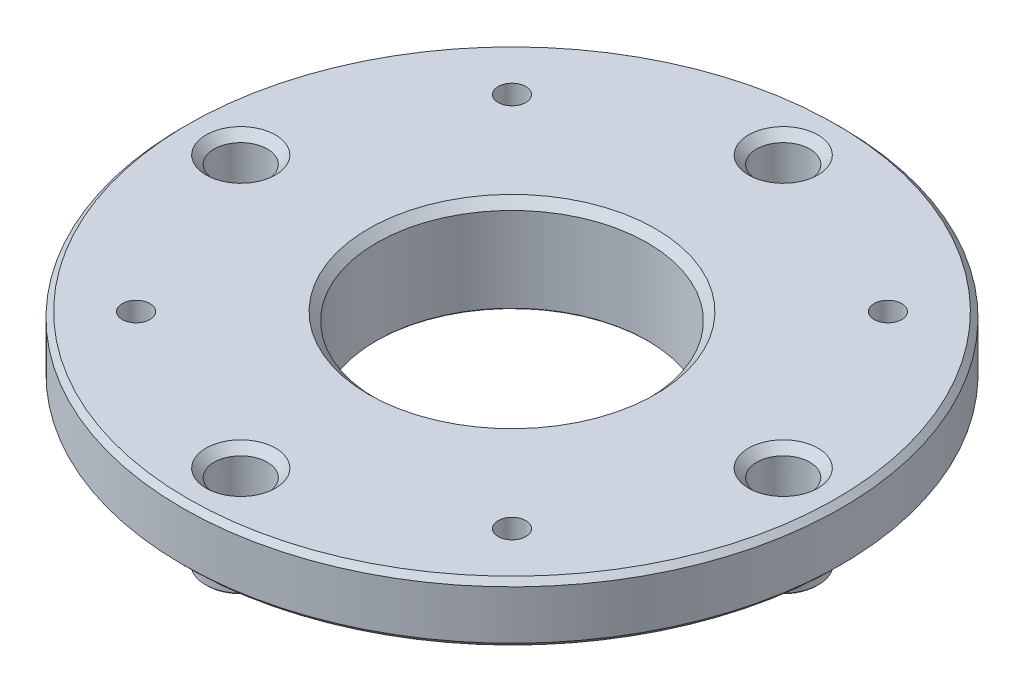
SolidWorks part; units mm, degrees
ref_plane "Front Plane" through (0, 0, 0) normal (0, 0, 1) x (1, 0, 0)
ref_plane "Top Plane" through (0, 0, 0) normal (0, 1, 0) x (1, 0, 0)
ref_plane "Right Plane" through (0, 0, 0) normal (1, 0, 0) x (0, 0, -1)
sketch "Sketch1" plane through (0, 0, 0) normal (0, 0, 1) x (1, 0, 0)
  line L0 (60.75, 11) -> (0, 11)
  line L1 (0, 11) -> (0, 0)
  line L2 (0, 0) -> (60.75, 0)
  line L3 (60.75, 0) -> (60.75, 11)
  line L4 (0, 11) -> (0, 0) construction
revolve "Revolve1" add sketch "Sketch1" angle 360 about L4 reverse direction yes
sketch "Sketch2" plane through (0, 0, 0) normal (0, -1, 0) x (1, 0, 0)
  circle A0 centre (0, 0) radius 28.485
extrude "Boss-Extrude1" add sketch "Sketch2" along normal blind 6.35
ref_plane "Plane1" through (0, 0, 0) normal (0, 0, -1) x (-1, 0, 0)
sketch "Sketch3" plane through (0, 0, 0) normal (0, 0, -1) x (-1, 0, 0)
  line L0 (43.525, -4.65) -> (50, -4.65)
  line L1 (50, -4.65) -> (50, 0)
  line L2 (50, 0) -> (43.525, 0)
  line L3 (43.525, 0) -> (43.525, -4.65)
  line L4 (50, -4.65) -> (50, 0) construction
revolve "Revolve2" add sketch "Sketch3" angle 360 about L4 reverse direction yes
ref_plane "Plane2" through (0, 0, -50) normal (0, 0, -1) x (-1, 0, 0)
sketch "Sketch4" plane through (0, 0, -50) normal (0, 0, -1) x (-1, 0, 0)
  line L0 (-6.475, -4.65) -> (0, -4.65)
  line L1 (0, -4.65) -> (0, 0)
  line L2 (0, 0) -> (-6.475, 0)
  line L3 (-6.475, 0) -> (-6.475, -4.65)
  line L4 (0, -4.65) -> (0, 0) construction
revolve "Revolve3" add sketch "Sketch4" angle 360 about L4 reverse direction yes
sketch "Sketch5" plane through (0, 0, 0) normal (0, 0, -1) x (-1, 0, 0)
  line L0 (-56.475, -4.65) -> (-50, -4.65)
  line L1 (-50, -4.65) -> (-50, 0)
  line L2 (-50, 0) -> (-56.475, 0)
  line L3 (-56.475, 0) -> (-56.475, -4.65)
  line L4 (-50, -4.65) -> (-50, 0) construction
revolve "Revolve4" add sketch "Sketch5" angle 360 about L4 reverse direction yes
ref_plane "Plane3" through (0, 0, 50) normal (0, 0, -1) x (-1, 0, 0)
sketch "Sketch6" plane through (0, 0, 50) normal (0, 0, -1) x (-1, 0, 0)
  line L0 (-6.475, -4.65) -> (0, -4.65)
  line L1 (0, -4.65) -> (0, 0)
  line L2 (0, 0) -> (-6.475, 0)
  line L3 (-6.475, 0) -> (-6.475, -4.65)
  line L4 (0, -4.65) -> (0, 0) construction
revolve "Revolve5" add sketch "Sketch6" angle 360 about L4 reverse direction yes
hole_wizard "Hole1" positions "Sketch8" profile "Sketch7" legacy
sketch "Sketch8" plane through (0, 11, 0) normal (0, 1, 0) x (1, 0, 0)
  point P0 (-34.6482, -34.6482)
  point P1 (34.6482, -34.6482)
  point P2 (34.6482, 34.6482)
  point P3 (-34.6482, 34.6482)
sketch "Sketch7" plane through (-34.6482, 11, 34.6482) normal (1, 0, 0) x (0, 0, 1)
  line L0 (0, 0) -> (0, 17.35)
  line L1 (0, 17.35) -> (2.5527, 17.35)
  line L2 (2.5527, 17.35) -> (2.5527, 0)
  line L3 (2.5527, 0) -> (0, 0)
  line L4 (0, 110) -> (0, -10) construction
  dimension "Diameter" = 5.1054
  dimension "Depth" = 17.35
hole_wizard "M8 Clearance Hole1" positions "Sketch10" profile "Sketch9" hole size "M8" standard "ANSI Metric"
sketch "Sketch10" plane through (0, 11, 0) normal (0, 1, 0) x (1, 0, 0)
  point P0 (50, 0)
  point P1 (0, -50)
  point P2 (-50, 0)
sketch "Sketch9" plane through (50, 11, 0) normal (1, 0, 0) x (0, 0, 1)
  line L0 (0, 0) -> (0, 17.35)
  line L1 (0, 17.35) -> (4.9022, 17.35)
  line L2 (4.9022, 17.35) -> (4.9022, 0)
  line L5 (4.9022, 0) -> (0, 0)
  line L11 (0, -6.35) -> (0, 107.95) construction
  dimension "Thru Hole Dia." = 9.8044
  dimension "Thru Hole Depth" = 17.35
hole_wizard "M45 Clearance Hole1" positions "Sketch12" profile "Sketch11" hole size "M45" standard "ANSI Metric"
sketch "Sketch12" plane through (0, 11, 0) normal (0, 1, 0) x (1, 0, 0)
  point P0 (0, 0)
sketch "Sketch11" plane through (0, 11, 0) normal (1, 0, 0) x (0, 0, 1)
  line L0 (0, 0) -> (0, 17.35)
  line L1 (0, 17.35) -> (24.9555, 17.35)
  line L2 (24.9555, 17.35) -> (24.9555, 0)
  line L5 (24.9555, 0) -> (0, 0)
  line L11 (0, -6.35) -> (0, 107.95) construction
  dimension "Thru Hole Dia." = 49.911
  dimension "Thru Hole Depth" = 17.35
hole_wizard "M8 Clearance Hole2" positions "Sketch14" profile "Sketch13" hole size "M8" standard "ANSI Metric"
sketch "Sketch14" plane through (0, -4.65, 0) normal (0, -1, 0) x (-1, 0, 0)
  point P0 (0, 50)
sketch "Sketch13" plane through (0, -4.65, -50) normal (1, 0, 0) x (0, 0, -1)
  line L0 (0, 0) -> (0, 15.65)
  line L1 (0, 15.65) -> (4.9022, 15.65)
  line L2 (4.9022, 15.65) -> (4.9022, 0)
  line L5 (4.9022, 0) -> (0, 0)
  line L11 (0, -6.35) -> (0, 107.95) construction
  dimension "Thru Hole Dia." = 9.8044
  dimension "Thru Hole Depth" = 15.65
chamfer "Chamfer1" distance 0.25 angle 45 9 edges at (0, -6.35, 24.9555) (0, -4.65, 45.0978) (-50, -4.65, -4.9022) (50, -4.65, -4.9022) (-50, -4.65, 6.475) (0, -4.65, 56.475) (50, -4.65, 6.475) (0, -4.65, -54.9022) (0, -4.65, -43.525)
chamfer "Chamfer2" distance 1 angle 45 3 edges at (0, 11, -60.75) (0, 0, -60.75) (0, -6.35, -28.485)
chamfer "Chamfer3" distance 1.5 angle 45 5 edges at (0, 11, -54.9022) (50, 11, 4.9022) (0, 11, 24.9555) (0, 11, 54.9022) (-50, 11, 4.9022)
